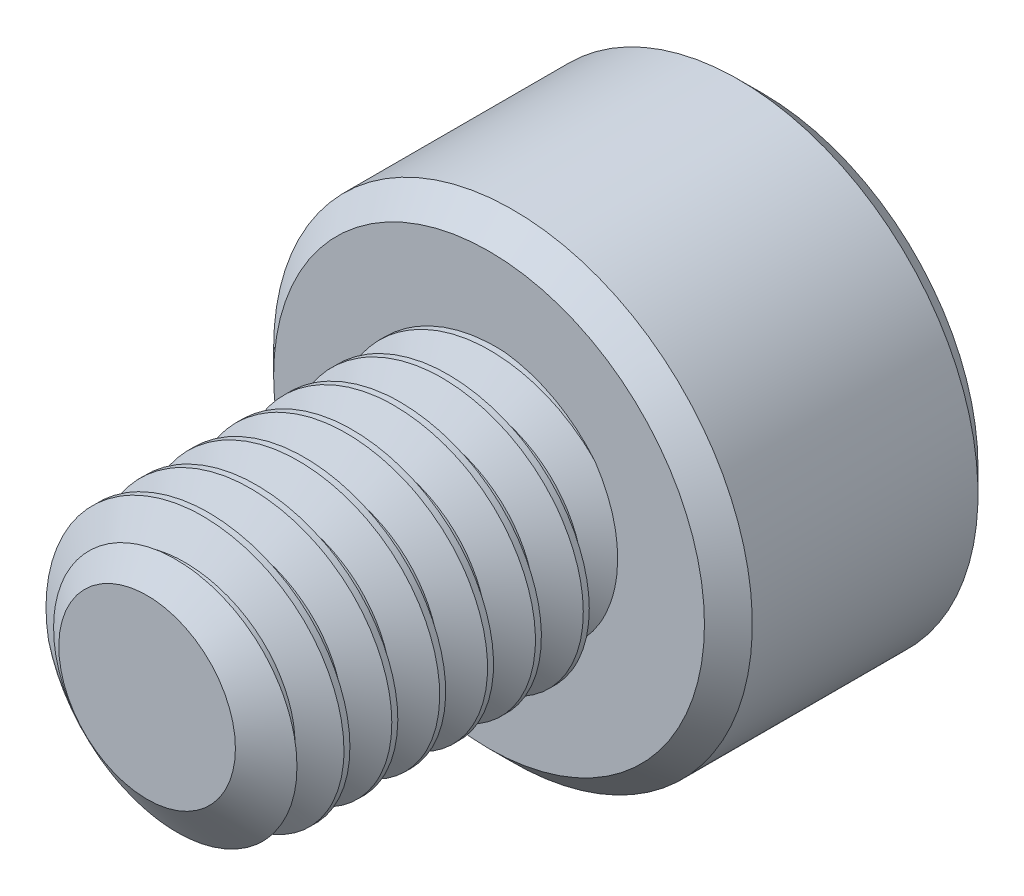
SolidWorks part; units mm, degrees
other "DetailItem1"
ref_plane "Front Plane" through (0, 0, 0) normal (0, 0, 1) x (1, 0, 0)
ref_plane "Top Plane" through (0, 0, 0) normal (0, 1, 0) x (1, 0, 0)
ref_plane "Right Plane" through (0, 0, 0) normal (1, 0, 0) x (0, 0, -1)
sketch "Sketch1" plane through (0, 0, 0) normal (0, 0, 1) x (1, 0, 0)
  circle A0 centre (0, 0) radius 2
  dimension "OD" = 4
extrude "Extrude1" add sketch "Sketch1" against normal blind 5
sketch "Sketch2" plane through (0, 0, 0) normal (0, 0, 1) x (1, 0, 0)
  circle A0 centre (0, 0) radius 2 construction
  circle A1 centre (0, 0) radius 2
curve "Helix/Spiral1" pitch 0.7 height 5.7 radius 2 centre (0, 0, 0) axis (0, 0, -1) start towards (0, 1, 0) parameters "pitch"=0.7
sketch "Sketch3" plane through (0, 0, 0) normal (1, 0, 0) x (0, 0, -1)
  line L0 (-0.6125, 2) -> (-0.35, 1.5453)
  line L1 (-0.35, 1.5453) -> (-0.2625, 1.5453)
  line L2 (-0.2625, 1.5453) -> (0, 2)
  line L3 (-0.6125, 2) -> (0, 2)
  line L4 (-0.3062, 2) -> (-0.3062, 1.5453) construction
  line L5 (-0.4812, 1.7727) -> (-0.1312, 1.7727) construction
  line L6 (0, 2) -> (0, -2) construction
  dimension "D1" = 0.0875
  dimension "D2" = 0.35
  dimension "D3" = 60
sweep "Cut-Sweep1" cut profiles "Sketch3" path "Helix/Spiral1" align with end faces yes
sketch "Sketch4" plane through (0, 0, 0) normal (1, 0, 0) x (0, 0, -1)
  line L0 (0.4962, 2) -> (0, 1.2913)
  line L1 (0, 1.2913) -> (0, 2)
  line L2 (0.4962, 2) -> (0, 2)
  line L3 (-0.6125, 2) -> (0, 2) construction
  line L4 (0, 0) -> (7.0209, 0) construction
  dimension "D1" = 55
  dimension "D2" = 0.254
revolve "Cut-Revolve1" cut sketch "Sketch4" angle 360 about L4
sketch "Sketch6" plane through (0, 0, -5) normal (0, 0, -1) x (-1, 0, 0)
  circle A0 centre (0, 0) radius 3.5
  dimension "head dia" = 7
extrude "Extrude2" add sketch "Sketch6" along normal blind 4
sketch "Sketch7" plane through (0, 0, -9) normal (0, 0, -1) x (-1, 0, 0)
  line L1 (0, 1.7321) -> (-1.5, 0.866)
  line L2 (-1.5, 0.866) -> (-1.5, -0.866)
  line L3 (-1.5, -0.866) -> (0, -1.7321)
  line L4 (0, -1.7321) -> (1.5, -0.866)
  line L5 (1.5, -0.866) -> (1.5, 0.866)
  line L6 (1.5, 0.866) -> (0, 1.7321)
  circle A0 centre (0, 0) radius 1.5 construction
  dimension "hex dia" = 3
extrude "Cut-Extrude1" cut sketch "Sketch7" against normal blind 2.25
sketch "Sketch8" plane through (0, 0, -9) normal (0, 0, -1) x (-1, 0, 0)
  circle A0 centre (0, 0) radius 1.7321
extrude "Cut-Extrude2" cut sketch "Sketch8" against normal through all draft 45
chamfer "Chamfer1" distance 0.35 angle 45 2 edges at (-3.5, 0, -9) (-3.5, 0, -5)
sketch "Sketch10" plane through (0, 0, -5) normal (0, 0, 1) x (1, 0, 0)
  circle A1 centre (0, 0) radius 2
  circle A2 centre (0, 0) radius 2
  dimension "D1" = 0
ref_plane "Plane1" through (0, 0, 0) normal (0, 0, 1) x (1, 0, 0)
extrude "partial thread" [suppressed] add sketch "Sketch10" along normal up to surface (10 mm away) separate body up to plane "Plane1"
chamfer "Chamfer2" [suppressed] distance 0.08 angle 45
combine bodies "Combine1" [suppressed] operation type add bodies to combine 107 108
sketch "Sketch9" plane through (0, 0, 0) normal (1, 0, 0) x (0, 0, -1)
  line L0 (0, 2) -> (0, -2) construction
  line L1 (1.75, 2) -> (1.75, -2) construction
  dimension "D1" = 1.75
equation "\"D3@Helix/Spiral1\" = \"screw length@Extrude1\"+\"pitch@Helix/Spiral1\""
equation "\"D1@Sketch3\" = \"pitch@Helix/Spiral1\"*.125"
equation "\"D2@Sketch3\" = \"pitch@Helix/Spiral1\"*.5"
equation "\"D1@Cut-Extrude1\" = \"hex dia@Sketch7\"*.75"
equation "\"D1@Chamfer1\" = \"head dia@Sketch6\"*.05"
equation "\"D1@Sketch9\" = \"pitch@Helix/Spiral1\"*2.5"
equation "\"D1@Chamfer2\"=\"OD@Sketch1\"*.02"
